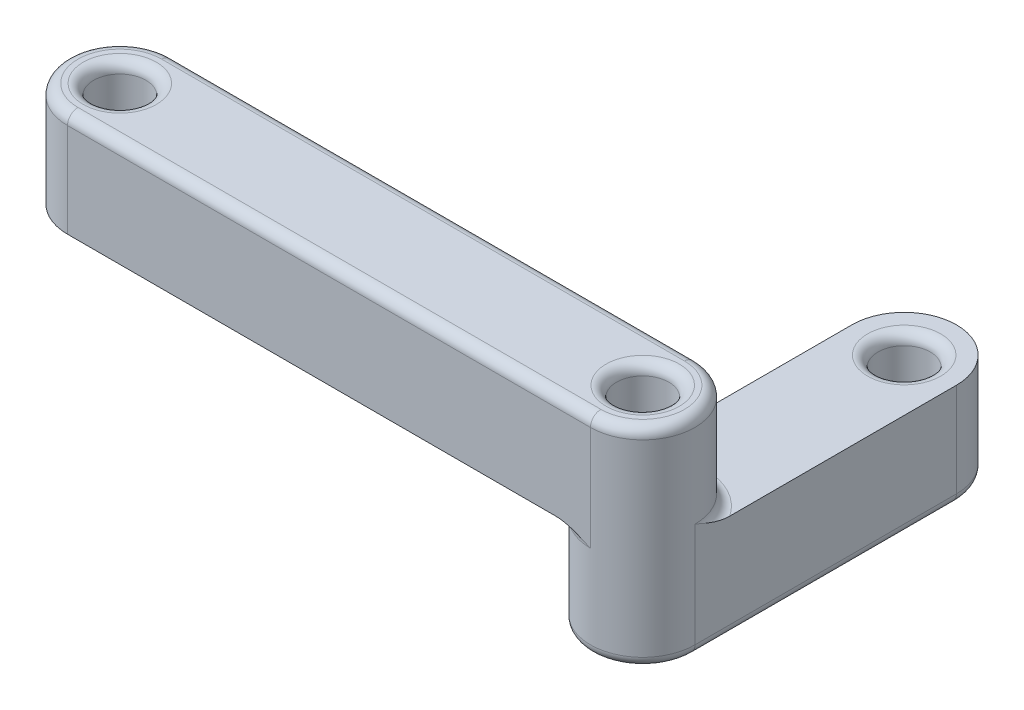
SolidWorks part; units mm, degrees
ref_plane "Front Plane" through (0, 0, 0) normal (0, 0, 1) x (1, 0, 0)
ref_plane "Top Plane" through (0, 0, 0) normal (0, 1, 0) x (1, 0, 0)
ref_plane "Right Plane" through (0, 0, 0) normal (1, 0, 0) x (0, 0, -1)
sketch "Sketch1" plane through (0, 0, 0) normal (0, 1, 0) x (1, 0, 0)
  line L0 (0, 0) -> (50, 0) construction
  line L1 (0, 5) -> (50, 5)
  line L2 (0, -5) -> (50, -5)
  arc A0 (0, 5) -> (0, -5) centre (0, 0) ccw
  arc A1 (50, -5) -> (50, 5) centre (50, 0) ccw
  circle A2 centre (0, 0) radius 2.5
  circle A3 centre (50, 0) radius 2.5
  point P3 (25, 0)
  dimension "D1" = 5
  dimension "D3" = 5
  dimension "D4" = 5
  dimension "D2" = 50
extrude "Boss-Extrude1" add sketch "Sketch1" along normal blind 10
sketch "Sketch2" plane through (0, 10, 0) normal (0, 1, 0) x (1, 0, 0)
  line L0 (50, 0) -> (50, 25) construction
  line L1 (45, 0) -> (45, 25)
  line L2 (55, 0) -> (55, 25)
  arc A0 (45, 0) -> (55, 0) centre (50, 0) ccw
  arc A1 (55, 25) -> (45, 25) centre (50, 25) ccw
  circle A2 centre (50, 0) radius 2.5
  circle A3 centre (50, 25) radius 2.5
  point P3 (50, 12.5)
  dimension "D1" = 5
  dimension "D3" = 5
  dimension "D2" = 25
extrude "Boss-Extrude2" add sketch "Sketch2" along normal blind 10
mirror "Mirror2" of "Boss-Extrude2", "Boss-Extrude1"
sketch "Sketch4" plane through (55, 0, 0) normal (1, 0, 0) x (0, 0, -1)
  line L0 (-5, 10) -> (-5, -10) construction
  line L1 (-5, 0) -> (30, 0)
  line L2 (-5, 0) -> (-5, 20)
  line L3 (-5, 20) -> (30, 20)
  line L4 (30, 0) -> (30, 20)
extrude "Cut-Extrude2" cut sketch "Sketch4" against normal blind 60
fillet "Fillet1" radius 1 12 edges at (50, -20, -22.5) (55, -20, -12.5) (50, -20, -30) (45, -20, -12.5) (50, -20, 5) (50, -20, 2.5) (-5, 0, 0) (25, 0, -5) (55, 0, 0) (25, 0, 5) (50, 0, -2.5) (0, 0, -2.5)
fillet "Fillet2" radius 1 2 edges at (53.5355, -10, -3.5355) (47.5, -10, -5)
fillet "Fillet3" radius 1 2 edges at (46.4645, -10, 3.5355) (45, -10, -2.5)
fillet "Fillet4" radius 1 1 edges at (50, -10, -22.5)
